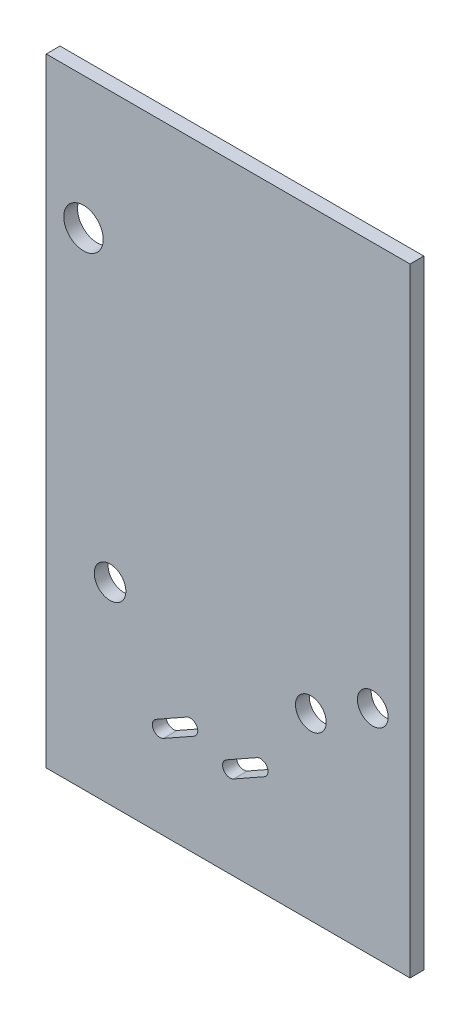
SolidWorks part; units mm, degrees
ref_plane "Front Plane" through (0, 0, 0) normal (0, 0, 1) x (1, 0, 0)
ref_plane "Top Plane" through (0, 0, 0) normal (0, 1, 0) x (1, 0, 0)
ref_plane "Right Plane" through (0, 0, 0) normal (1, 0, 0) x (0, 0, -1)
sketch "Sketch1" plane through (0, 0, 0) normal (0, 0, 1) x (1, 0, 0)
  line L0 (-41.4471, -70.4471) -> (-41.4471, 70.4471)
  line L1 (-26.2308, 73.6471) -> (38.6518, 73.6471)
  line L2 (-41.4471, 70.4471) -> (41.4471, 70.4471)
  line L3 (-44.6471, -70.649) -> (-44.6471, 70.649)
  line L4 (41.4471, 70.4471) -> (41.4471, -70.4471)
  line L5 (27.0934, -73.6471) -> (-41.649, -73.6471)
  line L6 (41.4471, -70.4471) -> (-41.4471, -70.4471)
  line L7 (-24.0867, 73.6955) -> (-35.6911, 73.6955)
  line L15 (-16.3293, -29.1587) -> (-16.3293, -23.8757)
  line L19 (44.6471, 67.6705) -> (44.6471, -53.896)
  line L20 (-0.4012, -48.3225) -> (6.5714, -44.4005)
  line L21 (8.2266, -47.343) -> (1.254, -51.2651)
  line L22 (-44.6471, 73.6471) -> (44.6471, 73.6471)
  line L23 (44.6471, 73.6471) -> (44.6471, -73.6471)
  line L24 (44.6471, -73.6471) -> (-44.6471, -73.6471)
  line L25 (-44.6471, -73.6471) -> (-44.6471, 73.6471)
  line L26 (-25.1679, 56.2163) -> (-25.1679, 10.288)
  line L27 (-25.1679, 10.288) -> (24.9222, 10.288)
  line L28 (24.9222, 10.288) -> (24.9222, 56.2163)
  line L29 (24.9222, 56.2163) -> (-25.1679, 56.2163)
  line L34 (36.6393, 62.5051) -> (-36.0272, 62.5051)
  line L35 (-38.5272, 60.0051) -> (-38.5272, 6.9331)
  line L36 (-36.0272, 4.4331) -> (29.8893, 4.4331)
  line L37 (39.1393, 13.6831) -> (39.1393, 60.0051)
  line L38 (-16.4012, -48.3225) -> (-9.4286, -44.4005)
  line L39 (-7.7734, -47.343) -> (-14.746, -51.2651)
  line L41 (44.6471, 70.649) -> (44.6471, 67.6705)
  line L43 (38.6518, 73.6471) -> (41.649, 73.6471)
  line L45 (-41.649, 73.6471) -> (-26.2308, 73.6471)
  line L150 (42.2525, -55.0539) -> (42.2511, -54.9499)
  circle A0 centre (34.1495, 24.0914) radius 10.7
  circle A2 centre (-26.9008, -26.5172) radius 3.6
  arc A3 (8.2266, -47.343) -> (6.5714, -44.4005) centre (7.399, -45.8717) ccw
  arc A6 (-16.4012, -48.3225) -> (-14.746, -51.2651) centre (-15.5736, -49.7938) ccw
  arc A7 (-7.7734, -47.343) -> (-9.4286, -44.4005) centre (-8.601, -45.8717) ccw
  circle A15 centre (18.8495, -29.5462) radius 3.5
  circle A16 centre (32.9602, -21.4767) radius 3.5
  arc A17 (-0.4012, -48.3225) -> (1.254, -51.2651) centre (0.4264, -49.7938) ccw
  circle A19 centre (-32.9539, 40.3411) radius 4.5
  arc A24 (39.1393, 60.0051) -> (36.6393, 62.5051) centre (36.6393, 60.0051) ccw
  arc A25 (-36.0272, 62.5051) -> (-38.5272, 60.0051) centre (-36.0272, 60.0051) ccw
  arc A26 (-38.5272, 6.9331) -> (-36.0272, 4.4331) centre (-36.0272, 6.9331) ccw
  arc A27 (29.8893, 4.4331) -> (39.1393, 13.6831) centre (29.8893, 13.6831) ccw
  ellipse E3 centre (-41.649, -70.649) end of major axis (-39.5276, -72.7703) minor radius 2.9963 (-44.6471, -70.649) -> (-41.649, -73.6471) ccw
  ellipse E5 centre (41.649, 70.649) end of major axis (39.5276, 72.7703) minor radius 2.9963 (44.6471, 70.649) -> (41.649, 73.6471) ccw
  ellipse E7 centre (-41.649, 70.649) end of major axis (-43.7703, 68.5276) minor radius 2.9963 (-41.649, 73.6471) -> (-44.6471, 70.649) ccw
  spline S1 degree 3 poles (44.6485, -54) (44.663, -55.258) (44.5568, -56.5068) (44.2157, -58.3662) (44.0715, -58.9837) (43.7192, -60.2138) (43.5128, -60.8202) (42.8075, -62.6008) (42.2221, -63.7422) (41.3373, -65.1085) (41.1525, -65.3788) (40.7717, -65.907) (40.5751, -66.1657) (39.9672, -66.9256) (39.1083, -67.8961) (38.1523, -68.7812) (37.1464, -69.6222) (36.6152, -70.0225) (34.9811, -71.1285) (33.8311, -71.748) (32.3187, -72.3766) (32.0124, -72.495) (31.3922, -72.7168) (31.0776, -72.8204) (30.1333, -73.105) (29.5001, -73.2613) (27.5898, -73.6337) (26.302, -73.7542) (25, -73.7456) knots 0 0 0 0 0.125 0.125 0.1875 0.1875 0.25 0.25 0.375 0.375 0.40625 0.40625 0.4375 0.4375 0.5 0.5625 0.5625 0.625 0.625 0.75 0.75 0.78125 0.78125 0.8125 0.8125 0.875 0.875 1 1 1 1
  dimension "D4" = 21.4
  dimension "D8" = 7
  dimension "D11" = 9
  dimension "D12" = 7.2
  dimension "D1" = 10.4977
  dimension "D2" = 89.2943
  dimension "D3" = 147.2943
  dimension "D5" = 25.9097
  dimension "D6" = 8.0696
  dimension "D7" = 14.1107
  dimension "D9" = 7.7861
  dimension "D10" = 22.1641
  dimension "D13" = 10.5715
  dimension "D14" = 3.2
extrude "Boss-Extrude1" add sketch "Sketch1" along normal blind 3.14 contours S1 L4 A0 L37 A27 L36 A26 L35 A25 L34 A24 L2 L0 L6 A17 L20 A3 L21 A16 A15 A7 L39 A6 L38 A2 | L36 A27 L37 A0 L28 L27 L26 L29 A24 L34 A25 L35 A26 A19 | A0 L28 L29 L26 L27 | L28 A0 | L37 A0 L28 | L4 A0 L37 | L4 S1 L6 region at (-0.5027, -20.7601, 0) region at (39.7509, -68.736, 0) region at (40.2573, 24.0914, 0) region at (30.9538, 35.3151, 0) region at (32.4596, 24.0914, 0) region at (-0.2381, 33.2953, 0) region at (24.3295, 24.0914, 0)
